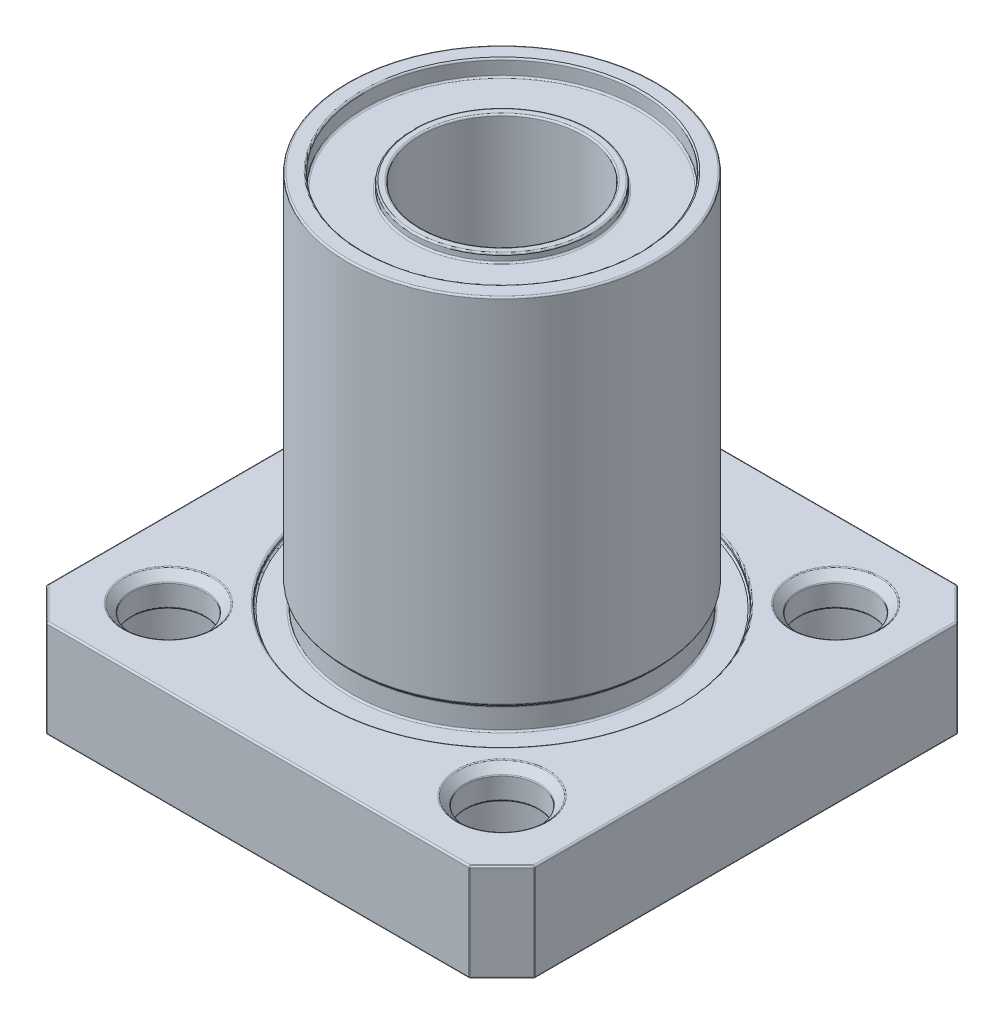
SolidWorks part; units mm, degrees
ref_plane "Front Plane" through (0, 0, 0) normal (0, 0, 1) x (1, 0, 0)
ref_plane "Top Plane" through (0, 0, 0) normal (0, 1, 0) x (1, 0, 0)
ref_plane "Right Plane" through (0, 0, 0) normal (1, 0, 0) x (0, 0, -1)
sketch "Sketch1" plane through (0, 0, 0) normal (0, 1, 0) x (1, 0, 0)
  line L1 (-15, -15) -> (15, -15)
  line L2 (-15, -15) -> (-15, 15)
  line L3 (-15, 15) -> (15, 15)
  line L4 (15, -15) -> (15, 15)
  line L5 (-15, -15) -> (15, 15) construction
  line L6 (-15, 15) -> (15, -15) construction
  point P0 (0, 0)
  dimension "D1" = 30
extrude "Boss-Extrude1" add sketch "Sketch1" along normal blind 6
sketch "Sketch2" plane through (0, 6, 0) normal (0, 1, 0) x (1, 0, 0)
  line L0 (15, -15) -> (15, 15) construction
  circle A0 centre (0, 0) radius 9.5
  dimension "D1" = 19
extrude "Boss-Extrude2" add sketch "Sketch2" along normal blind 23
sketch "Sketch3" plane through (0, 6, 0) normal (0, 1, 0) x (1, 0, 0)
  line L0 (-15, 15) -> (15, -15) construction
  line L1 (-15, -15) -> (15, 15) construction
  circle A0 centre (-10.253, 10.253) radius 2.25
  circle A1 centre (10.253, 10.253) radius 2.25
  circle A2 centre (10.253, -10.253) radius 2.25
  circle A3 centre (-10.253, -10.253) radius 2.25
  dimension "D1" = 4.5
extrude "Cut-Extrude3" cut sketch "Sketch3" against normal up to next
chamfer "Chamfer2" distance 2 angle 45 4 edges at (15, 3, -15) (15, 3, 15) (-15, 3, 15) (-15, 3, -15)
sketch "Sketch6" plane through (0, 29, 0) normal (0, 1, 0) x (1, 0, 0)
  circle A0 centre (0, 0) radius 8.5
  circle A1 centre (0, 0) radius 9.5 construction
  dimension "D1" = 1
extrude "Cut-Extrude4" cut sketch "Sketch6" against normal through all
sketch "Sketch7" plane through (0, 6, 0) normal (0, 1, 0) x (1, 0, 0)
  line L0 (-15, 15) -> (15, -15) construction
  circle A0 centre (0, 0) radius 10.8
  circle M5 centre (0, 0) radius 9.5
  dimension "D1" = 21.6
extrude "Cut-Extrude6" cut sketch "Sketch7" against normal blind 0.3 contours A0 M5 region at (-10.4945, 6, 0)
ref_axis "Axis2" through (0, 29, 0) along (0, -1, 0)
sketch "Sketch8" plane through (0, 0, 0) normal (0, 0, 1) x (1, 0, 0)
  line L0 (-9.5, 7.3) -> (-9.5, 5.7)
  line L1 (-9.5, 29) -> (-9.5, 5.7) construction
  line L2 (-9.5, 5.7) -> (-9.25, 5.7)
  line L3 (-9.25, 5.7) -> (-9.25, 7.05)
  line L4 (-9.25, 7.05) -> (-9.5, 7.3)
  line L5 (9.5, 6) -> (-9.5, 6) construction
  dimension "D1" = 1.6
  dimension "D2" = 0.25
  dimension "D3" = 0.25
  dimension "D4" = 0.3
revolve "Cut-Revolve1" cut sketch "Sketch8" angle 360 about axis through (0, 29, 0) along (0, -1, 0)
ref_plane "Plane1" through (0, 28, 0) normal (0, 1, 0) x (1, 0, 0)
sketch "Sketch9" plane through (0, 28, 0) normal (0, 1, 0) x (1, 0, 0)
  line L0 (-15, 15) -> (15, -15) construction
  circle A0 centre (0, 0) radius 8.5
  circle A1 centre (0, 0) radius 5
  dimension "D1" = 10
extrude "Boss-Extrude3" add sketch "Sketch9" against normal blind 27
sketch "Sketch10" plane through (0, 28, 0) normal (0, 1, 0) x (1, 0, 0)
  line L0 (-15, 15) -> (15, -15) construction
  circle A0 centre (0, 0) radius 5
  circle A1 centre (0, 0) radius 5.5
  dimension "D1" = 0.5
extrude "Boss-Extrude4" add sketch "Sketch10" along normal blind 0.5
chamfer "Chamfer3" distance 0.5 angle 45 4 edges at (10.253, 6, 12.503) (10.253, 6, -8.003) (-10.253, 6, 12.503) (-10.253, 6, -8.003)
sketch "Sketch12" plane through (0, 0, 0) normal (0, -1, 0) x (1, 0, 0)
  line L0 (-15, -15) -> (15, 15) construction
  line L1 (-15, 15) -> (15, -15) construction
  circle A0 centre (-10.253, 10.253) radius 3.75
  circle A1 centre (10.253, 10.253) radius 3.75
  circle A2 centre (-10.253, -10.253) radius 3.75
  circle A3 centre (10.253, -10.253) radius 3.75
  dimension "D1" = 7.5
extrude "Cut-Extrude7" cut sketch "Sketch12" against normal blind 4.1
fillet "Fillet2" radius 0.1 49 edges at (0, 1, 8.5) (-15, 0, 0) (14, 0, 14) (15, 3, 13) (15, 0, 0) (14, 0, -14) (15, 3, -13) (0, 0, -15) (13, 3, -15) (-15, 3, -13) (-14, 0, -14) (-13, 3, -15) (-14, 0, 14) (-15, 3, 13) (-13, 3, 15) (13, 3, 15) (0, 0, 15) (-10.253, 4.1, -12.503) (-10.253, 5.5, -12.503) (10.253, 4.1, 8.003) (10.253, 5.5, 8.003) (-10.253, 4.1, 8.003) (-10.253, 5.5, 8.003) (10.253, 4.1, -12.503) (10.253, 5.5, -12.503) (14, 6, 14) (0, 6, 15) (-14, 6, 14) (-15, 6, 0) (-14, 6, -14) (0, 6, -15) (14, 6, -14) (15, 6, 0) (0, 6, 10.8) (-10.253, 6, -13.003) (-10.253, 6, 7.503) (10.253, 6, -13.003) (10.253, 6, 7.503) (0, 5.7, 10.8) (0, 7.3, 9.5) (0, 5.7, 9.25) (0, 7.05, 9.25) (0, 29, 9.5) (0, 29, 8.5) (0, 28, 5.5) (0, 28, 8.5) (0, 28.5, 5.5) (0, 28.5, 5) (0, 0, 8.5)
chamfer "Chamfer4" distance 0.5 angle 45 4 edges at (-10.253, 0, -14.003) (10.253, 0, -14.003) (10.253, 0, 6.503) (-10.253, 0, 6.503)
